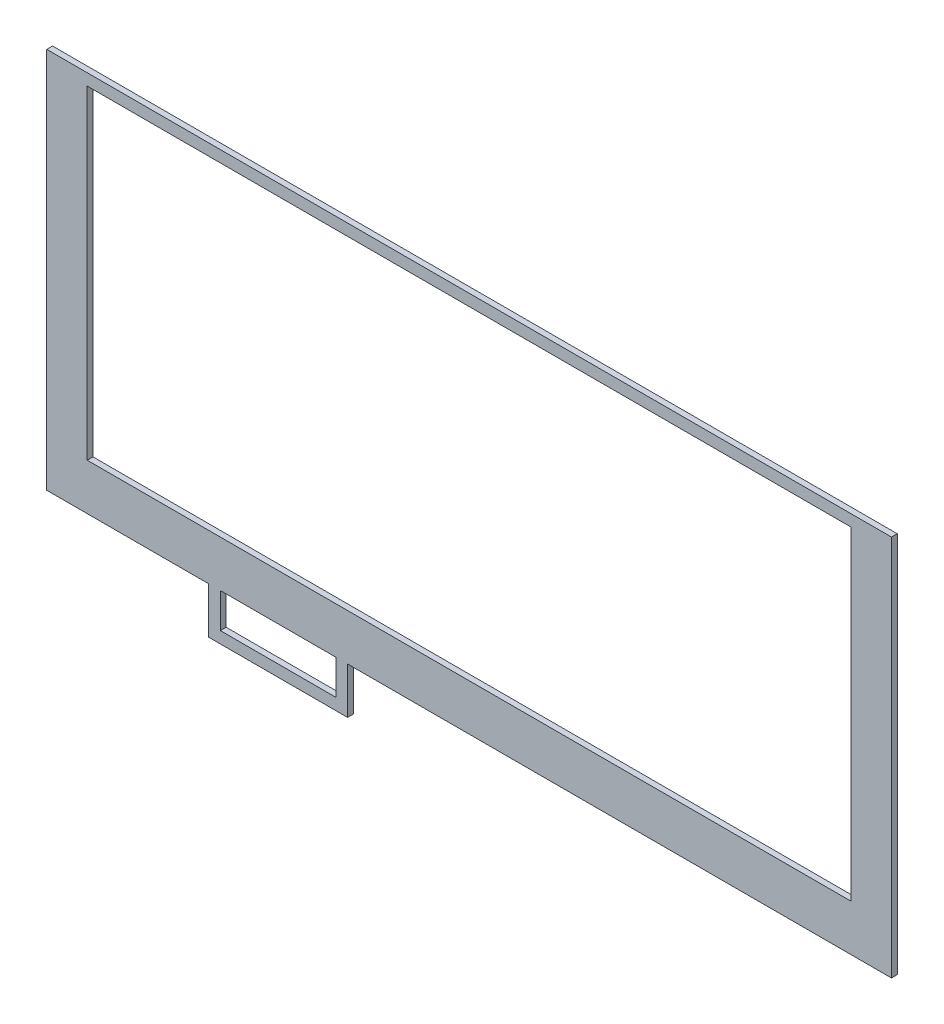
SolidWorks part; units mm, degrees
ref_plane "Alzado" through (0, 0, 0) normal (0, 0, 1) x (1, 0, 0)
ref_plane "Planta" through (0, 0, 0) normal (0, 1, 0) x (1, 0, 0)
ref_plane "Vista lateral" through (0, 0, 0) normal (1, 0, 0) x (0, 0, -1)
sketch "Croquis2" plane through (0, 0, 0) normal (0, 0, 1) x (1, 0, 0)
  line L1 (-365, -165) -> (365, -165)
  line L2 (-365, -165) -> (-365, 165)
  line L3 (-365, 165) -> (365, 165)
  line L4 (365, -165) -> (365, 165)
  line L5 (-365, -165) -> (365, 165) construction
  line L6 (-365, 165) -> (365, -165) construction
  point P0 (0, 0)
  dimension "D1" = 730
  dimension "D2" = 330
extrude "Saliente-Extruir2" add sketch "Croquis2" along normal blind 5
sketch "Croquis4" plane through (0, 0, 5) normal (0, 0, 1) x (1, 0, 0)
  line L0 (365, 165) -> (-365, 165) construction
  line L1 (330, 155) -> (-330, 155)
  line L2 (330, 155) -> (330, -125)
  line L3 (330, -125) -> (-330, -125)
  line L4 (-330, 155) -> (-330, -125)
  line L5 (365, -165) -> (365, 165) construction
  line L6 (-365, 165) -> (-365, -165) construction
  line L7 (-365, -165) -> (365, -165) construction
  dimension "D1" = 10
  dimension "D2" = 35
  dimension "D3" = 35
  dimension "D4" = 40
  dimension "D5" = 660
  dimension "D6" = 280
extrude "Cortar-Extruir1" cut sketch "Croquis4" against normal up to surface (5 mm away) up to face at (0, 0, 0)
sketch "Croquis5" plane through (0, 0, 5) normal (0, 0, 1) x (1, 0, 0)
  line L0 (-365, -165) -> (365, -165) construction
  line L1 (-225, -165) -> (-105, -165)
  line L2 (-225, -165) -> (-225, -205)
  line L3 (-225, -205) -> (-105, -205)
  line L4 (-105, -165) -> (-105, -205)
  line L5 (-365, 165) -> (-365, -165) construction
  line L7 (-215, -165) -> (-115, -165)
  line L8 (-215, -165) -> (-215, -195)
  line L9 (-215, -195) -> (-115, -195)
  line L10 (-115, -165) -> (-115, -195)
  line M8 (-365, -165) -> (365, -165)
  dimension "D1" = 140
  dimension "D2" = 10
  dimension "D3" = 10
extrude "Saliente-Extruir3" add sketch "Croquis5" against normal up to surface (5 mm away) contours L10 L9 L8 L2 L3 L4 M8 region at (-220, -166.2649, 5) up to face at (0, 15, 0)
